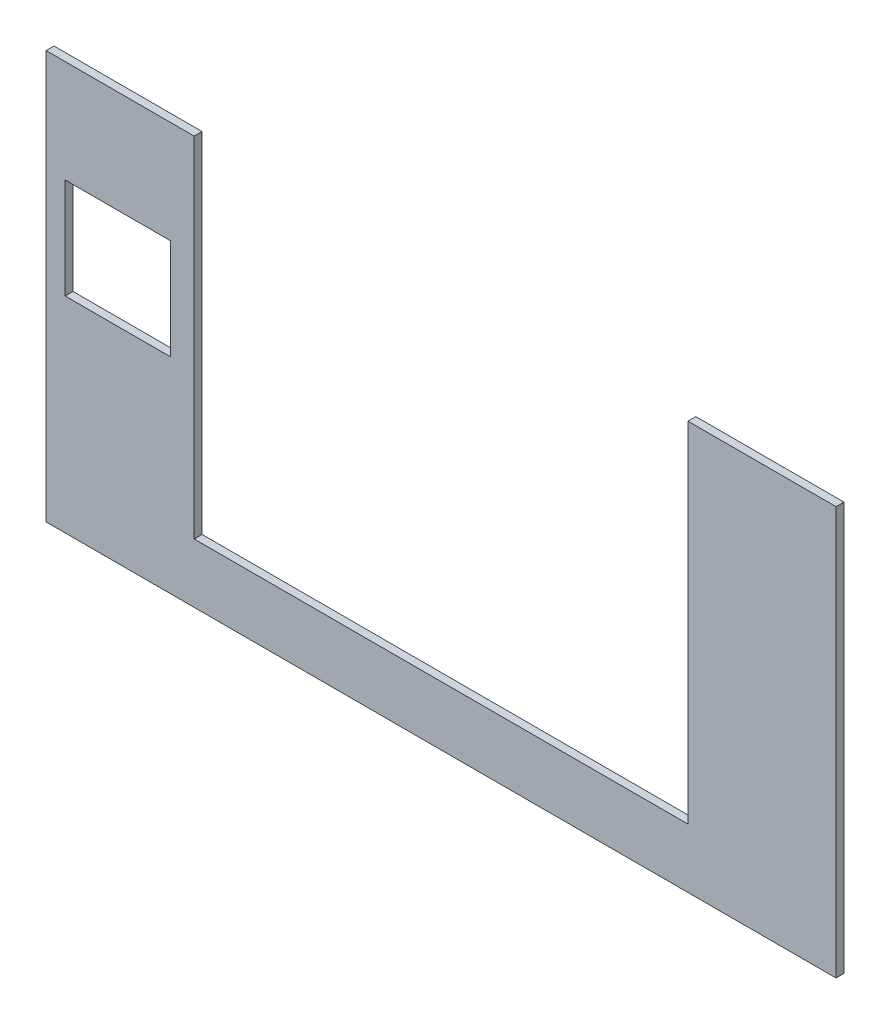
SolidWorks part; units mm, degrees
ref_plane "Front" through (0, 0, 0) normal (0, 0, 1) x (1, 0, 0)
ref_plane "Top" through (0, 0, 0) normal (0, 1, 0) x (1, 0, 0)
ref_plane "Right" through (0, 0, 0) normal (1, 0, 0) x (0, 0, -1)
sketch "Эскиз1" plane through (0, 0, 0) normal (0, 0, 1) x (1, 0, 0)
  line L0 (-592.6187, -146.0099) -> (-480.1187, -146.0099)
  line L1 (-1080.1187, -146.0099) -> (-967.6187, -146.0099)
  line L2 (-1080.1187, -146.0099) -> (-1080.1187, -456.0099)
  line L3 (-1080.1187, -456.0099) -> (-480.1187, -456.0099)
  line L4 (-480.1187, -146.0099) -> (-480.1187, -456.0099)
  line L6 (-967.6187, -146.0099) -> (-967.6187, -411.0099)
  line L7 (-967.6187, -411.0099) -> (-592.6187, -411.0099)
  line L8 (-592.6187, -146.0099) -> (-592.6187, -411.0099)
  line L9 (-780.1187, -456.0099) -> (-780.1187, 62.7649) construction
  point P10 (-780.1187, -411.0099)
  dimension "D1" = 375
  dimension "D2" = 600
  dimension "D3" = 310
  dimension "D4" = 265
extrude "Бобышка-Вытянуть1" add sketch "Эскиз1" along normal blind 6
sketch "Эскиз2" plane through (0, 0, 0) normal (0, 0, -1) x (-1, 0, 0)
  line L0 (1080.1187, -146.0099) -> (1080.1187, -456.0099) construction
  line L1 (985.6304, -223.8538) -> (1065.6304, -223.8538)
  line L2 (985.6304, -223.8538) -> (985.6304, -300.1909)
  line L3 (985.6304, -300.1909) -> (1065.6304, -300.1909)
  line L4 (1065.6304, -223.8538) -> (1065.6304, -300.1909)
  dimension "D1" = 80
  dimension "D2" = 14.4882
extrude "Вырез-Вытянуть1" cut sketch "Эскиз2" against normal up to surface (6 mm away) up to face at (-780.1187, -289.7599, 6)
